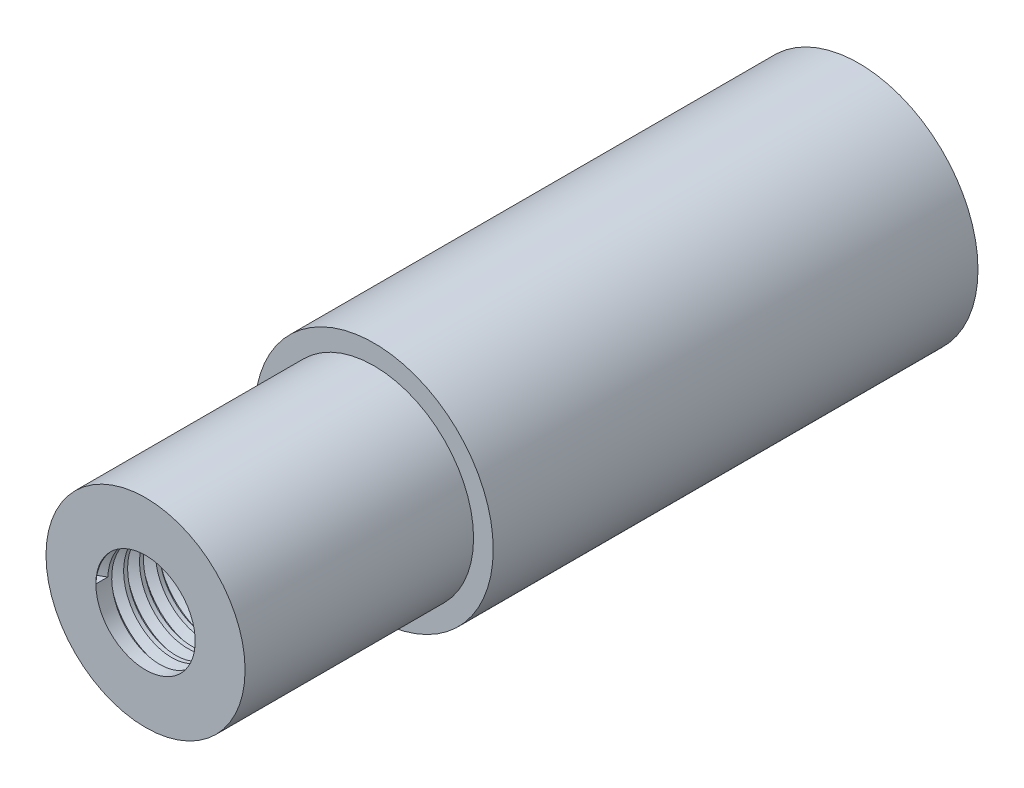
SolidWorks part; units mm, degrees
ref_plane "Front Plane" through (0, 0, 0) normal (0, 0, 1) x (1, 0, 0)
ref_plane "Top Plane" through (0, 0, 0) normal (0, 1, 0) x (1, 0, 0)
ref_plane "Right Plane" through (0, 0, 0) normal (1, 0, 0) x (0, 0, -1)
sketch "Sketch1" plane through (0, 0, 0) normal (0, 0, 1) x (1, 0, 0)
  circle A0 centre (0, 0) radius 6
  circle A1 centre (0, 0) radius 5.01
  dimension "D1" = 12
  dimension "D2" = 10.02
extrude "Boss-Extrude1" add sketch "Sketch1" along normal blind 24.4
sketch "Sketch2" plane through (0, 0, 24.4) normal (0, 0, 1) x (1, 0, 0)
  circle A0 centre (0, 0) radius 5.01 construction
  circle A1 centre (0, 0) radius 5.01
extrude "Boss-Extrude2" add sketch "Sketch2" along normal blind 11.5 separate body
sketch "Sketch3" plane through (0, 0, 35.9) normal (0, 0, 1) x (1, 0, 0)
  circle A0 centre (0, 0) radius 2.5
  dimension "D1" = 5
extrude "Cut-Extrude1" cut sketch "Sketch3" against normal up to surface (11.5 mm away) up to face at (6, 0, 24.4)
thread "Thread1" pitch 0.8 method cut profile "Thread Profile1" start angle 0, offset 0, length 0, pitch 0.8, diameter 5
ref_plane "Plane1" through (-2.5, 0, 35.9) normal (0, -1, 0) x (-1, 0, 0)
sketch "Thread Profile1" plane through (-2.5, 0, 35.9) normal (0, -1, 0) x (-1, 0, 0)
  line L0 (0, 0) -> (0, 0.8) construction
  line L1 (0, 0) -> (0.433, 0.25)
  line L2 (0.433, 0.25) -> (0.433, 0.35)
  line L3 (0.433, 0.35) -> (0, 0.6)
  line L4 (0.433, 0.3) -> (0, 0.3) construction
  line L11 (0, 0) -> (0, 0.6)
  point P2 (0, 0)
  dimension "Pitch" = 0.8
  dimension "Profile_Angle" = 60
  dimension "Profile_Land" = 0.1
  dimension "Profile_Height" = 0.433
sketch "Sketch8" plane through (0, 0, 24.4) normal (0, 0, -1) x (-1, 0, 0)
  circle A0 centre (0, 0) radius 5.01 construction
  circle A1 centre (0, 0) radius 5.01
  circle A2 centre (0, 0) radius 2.933
  dimension "D1" = 5.866
extrude "Boss-Extrude4" add sketch "Sketch8" along normal blind 22
